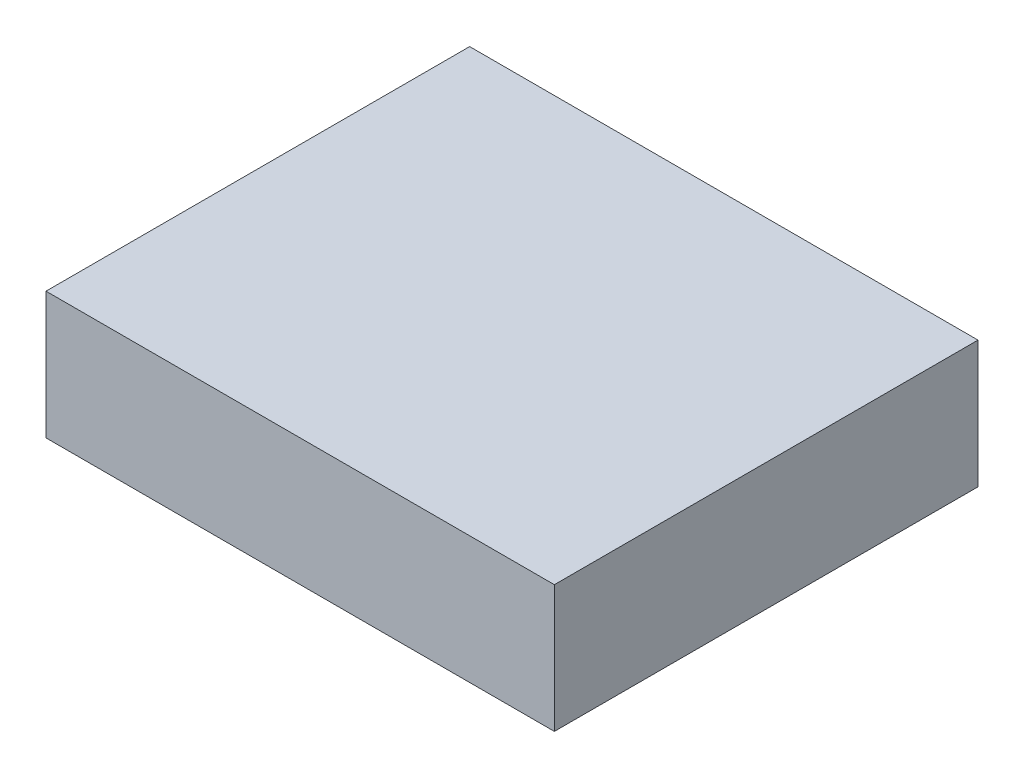
SolidWorks part; units mm, degrees
material "Cast Alloy Steel"
ref_plane "Front Plane" through (0, 0, 0) normal (1, 0, 0) x (0, 1, 0)
ref_plane "Top Plane" through (0, 0, 0) normal (0, 0, 1) x (0, 1, 0)
ref_plane "Right Plane" through (0, 0, 0) normal (0, 1, 0) x (-1, 0, 0)
sketch "Sketch1" plane through (0, 0, 0) normal (1, 0, 0) x (0, 1, 0)
  line L1 (0, -55) -> (0, 55) construction
  line L2 (-450, 150) -> (0, 150)
  line L3 (-450, 150) -> (-450, 0)
  line L4 (-450, 0) -> (0, 0)
  line L5 (0, 150) -> (0, 0)
  line L6 (0, 150) -> (150, 150)
  line L7 (0, 150) -> (0, 1150)
  line L8 (0, 1150) -> (150, 1150)
  line L9 (150, 150) -> (150, 1150)
  line L10 (-450, 0) -> (-600, 0)
  line L11 (-450, 0) -> (-450, -500)
  line L12 (-450, -500) -> (-600, -500)
  line L13 (-600, 0) -> (-600, -500)
  line L14 (55, 0) -> (-55, 0) construction
  dimension "D1" = 1000
  dimension "D2" = 150
  dimension "D3" = 150
  dimension "D4" = 150
  dimension "D5" = 450
  dimension "D6" = 500
  dimension "D7" = 0
  dimension "D8" = 0
extrude "Boss-Extrude2" add sketch "Sketch1" along normal blind 300 and the other way blind 300 contours L10 L13 L12 L11 region at (0, -525, -250)
